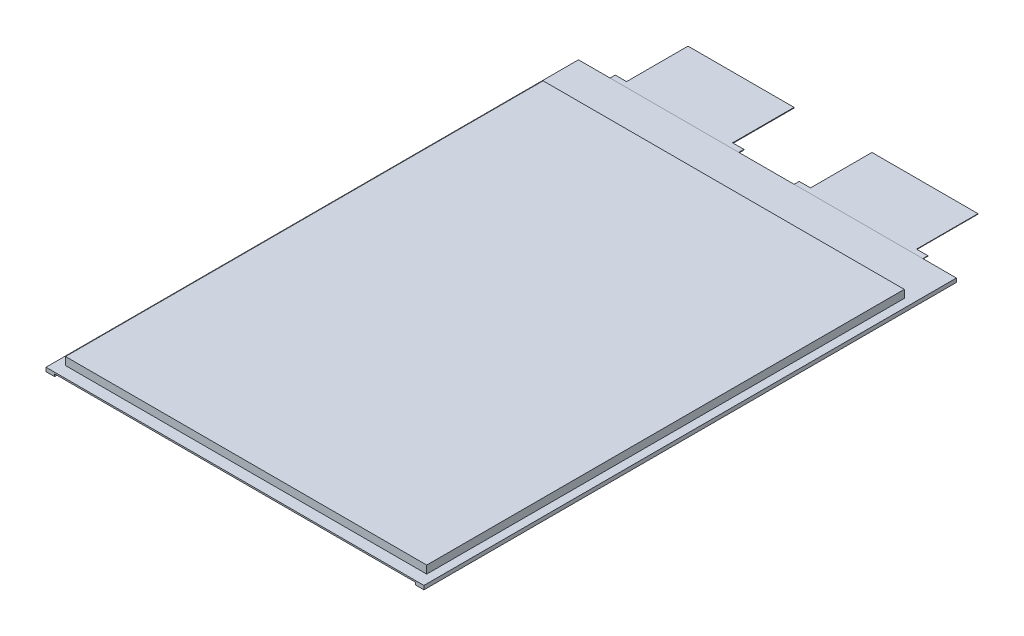
SolidWorks part; units mm, degrees
material "PE High Density"
ref_plane "Front Plane" through (0, 0, 0) normal (0, 0, 1) x (1, 0, 0)
ref_plane "Top Plane" through (0, 0, 0) normal (0, 1, 0) x (1, 0, 0)
ref_plane "Right Plane" through (0, 0, 0) normal (1, 0, 0) x (0, 0, -1)
sketch "Sketch1" plane through (0, 0, 0) normal (0, 1, 0) x (1, 0, 0)
  line L0 (80.5656, 0) -> (80.5656, 255.908) construction
  line L1 (0, 0) -> (161.1312, 0)
  line L2 (0, 0) -> (0, 227.0125)
  line L3 (0, 227.0125) -> (161.1312, 227.0125)
  line L4 (161.1312, 0) -> (161.1312, 227.0125)
  line L5 (3.5719, 4.7625) -> (157.5594, 4.7625)
  line L6 (3.5719, 4.7625) -> (3.5719, 208.3594)
  line L7 (3.5719, 208.3594) -> (157.5594, 208.3594)
  line L8 (157.5594, 4.7625) -> (157.5594, 208.3594)
  line L9 (119.1577, 255.5875) -> (119.1577, 218.1777) construction
  line L10 (18.1292, 227.0125) -> (63.3413, 227.0125)
  line L11 (18.1292, 227.0125) -> (18.1292, 255.5875)
  line L12 (18.1292, 255.5875) -> (63.3413, 255.5875)
  line L13 (63.3413, 227.0125) -> (63.3413, 255.5875)
  line L14 (96.5517, 227.0125) -> (141.7637, 227.0125)
  line L15 (96.5517, 227.0125) -> (96.5517, 255.5875)
  line L16 (96.5517, 255.5875) -> (141.7637, 255.5875)
  line L17 (141.7637, 227.0125) -> (141.7637, 255.5875)
  line L18 (91.7257, 227.0125) -> (146.5897, 227.0125)
  line L19 (91.7257, 227.0125) -> (91.7257, 229.3938)
  line L20 (91.7257, 229.3938) -> (146.5897, 229.3938)
  line L21 (146.5897, 227.0125) -> (146.5897, 229.3938)
  line L22 (40.7352, 255.5875) -> (40.7352, 214.782) construction
  line L24 (13.3032, 227.0125) -> (68.1673, 227.0125)
  line L25 (13.3032, 227.0125) -> (13.3032, 229.3938)
  line L26 (13.3032, 229.3938) -> (68.1673, 229.3938)
  line L27 (68.1673, 227.0125) -> (68.1673, 229.3938)
  dimension "D1" = 161.1312
  dimension "D2" = 227.0125
  dimension "D3" = 153.9875
  dimension "D4" = 203.5969
  dimension "D5" = 208.3594
  dimension "D6" = 19.3675
  dimension "D7" = 45.212
  dimension "D8" = 97.79
  dimension "D9" = 45.212
  dimension "D10" = 28.575
  dimension "D11" = 54.864
  dimension "D12" = 2.3813
  dimension "D13" = 2.3813
  dimension "D14" = 54.864
extrude "Cell Insulation" add sketch "Sketch1" along normal mid plane 0.635 contours L0 L1 L4 L3 L7 L8 L5 | L1 L0 L5 L6 L7 L3 L2 region at (2.7838, 0, -113.5063)
extrude "Cell Body" add sketch "Sketch1<3>" along normal blind 3.6703 and the other way blind 3.4163 contours L5 L0 L7 L6 | L0 L5 L8 L7 region at (80.5656, 0, -106.5609)
sketch "Sketch1<3>" plane through (0, 0, 0) normal (0, 1, 0) x (1, 0, 0) same geometry as "Sketch1"
extrude "Anode Tab" add sketch "Sketch1<4>" along normal mid plane 0.2032 contours L3 L17 L16 L15 | L20 L19 L3 L15 | L20 L15 L3 L17 | L3 L21 L20 L17 region at (144.1767, 0, -228.2031) region at (119.1577, 0, -228.2031) region at (94.1387, 0, -228.2031) region at (119.1577, 0, -242.4906)
sketch "Sketch1<4>" plane through (0, 0, 0) normal (0, 1, 0) x (1, 0, 0) same geometry as "Sketch1"
extrude "Cathode Tab" add sketch "Sketch1<5>" along normal mid plane 0.2794 contours L3 L13 L12 L11 | L26 L25 L3 L11 | L26 L11 L3 L13 | L3 L27 L26 L13 region at (15.7162, 0, -228.2031) region at (40.7353, 0, -228.2031) region at (65.7543, 0, -228.2031) region at (40.7353, 0, -242.4906)
sketch "Sketch1<5>" plane through (0, 0, 0) normal (0, 1, 0) x (1, 0, 0) same geometry as "Sketch1"
sketch "Sketch2" plane through (0, -0.3175, 0) normal (0, -1, 0) x (1, 0, 0)
  line L0 (0, 0) -> (161.1312, 0) construction
  line L1 (0, -227.0125) -> (3.683, -227.0125)
  line L2 (0, -227.0125) -> (0, 0)
  line L3 (0, 0) -> (3.683, 0)
  line L4 (3.683, -227.0125) -> (3.683, 0)
  dimension "D1" = 3.683
extrude "Edge Fold" add sketch "Sketch2" along normal blind 1.016
ref_plane "Mirror Plane" through (80.5656, 0, 0) normal (-1, 0, 0) x (0, 0, 1)
mirror "Edge Folds Mirror" about plane through (80.5656, 0, 0) normal (-1, 0, 0) of "Edge Fold"
sketch "Sketch4" plane through (0, -3.4163, 0) normal (0, -1, 0) x (1, 0, 0)
  line L0 (157.5594, -208.3594) -> (3.5719, -4.7625)
  point P4 (80.5656, -106.5609)
